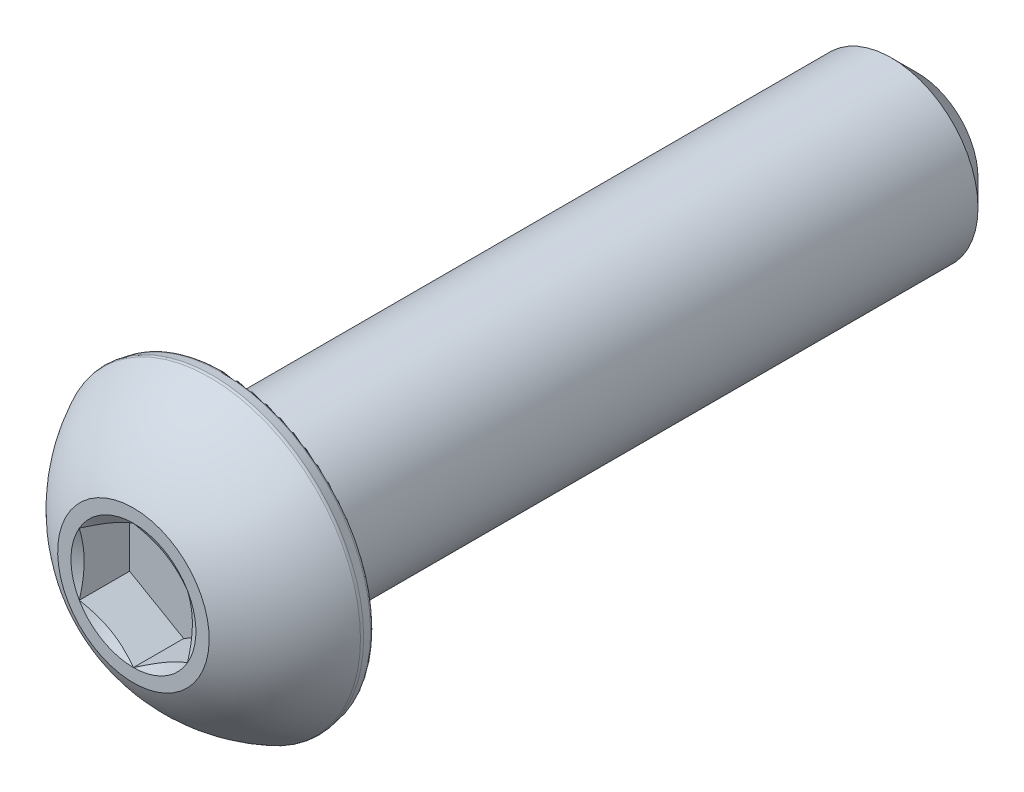
SolidWorks part; units mm, degrees
material "Cast Alloy Steel"
ref_plane "Front Plane" through (0, 0, 0) normal (0, 0, 1) x (1, 0, 0)
ref_plane "Top Plane" through (0, 0, 0) normal (0, 1, 0) x (1, 0, 0)
ref_plane "Right Plane" through (0, 0, 0) normal (1, 0, 0) x (0, 0, -1)
sketch "Sketch1" plane through (0, 0, 0) normal (1, 0, 0) x (0, 0, -1)
  line L0 (-14.3764, 0) -> (14.3764, 0) construction
  line L1 (-14.3764, 0) -> (-14.3764, 5.5499)
  line L2 (-14.3764, 5.5499) -> (-11.0236, 5.5499)
  line L3 (-11.0236, 5.5499) -> (-11.0236, 3.175)
  line L4 (-11.0236, 3.175) -> (14.3764, 3.175)
  line L5 (14.3764, 3.175) -> (14.3764, 0)
  point P2 (0, 0)
  point P4 (13.1064, 0)
  point P9 (12.4714, 3.175)
  point P10 (12.4714, -3.175)
  point P11 (14.3764, -3.175)
  point P15 (-12.5324, 0)
  dimension "Head Height" = 3.3528
  dimension "Head Diameter" = 11.0998
  dimension "Length" = 25.4
  dimension "Screw Size Decimal Equivalent" = 6.35
  dimension "Thread Pitch" = 1.27
  dimension "D1" = 1.905
  dimension "D2" = 1.844
sketch "Sketch2" plane through (0, 0, 0) normal (0, 0, 1) x (1, 0, 0)
  line L0 (0, 3.175) -> (0, 0) construction
  line L1 (0, 2.2914) -> (-1.9844, 1.1457)
  line L2 (-1.9844, 1.1457) -> (-1.9844, -1.1457)
  line L3 (-1.9844, -1.1457) -> (0, -2.2914)
  line L4 (0, -2.2914) -> (1.9844, -1.1457)
  line L5 (1.9844, -1.1457) -> (1.9844, 1.1457)
  line L6 (1.9844, 1.1457) -> (0, 2.2914)
  circle A0 centre (0, 0) radius 1.9844 construction
  circle A1 centre (0, 0) radius 2.7781
  point P10 (0, 2.7781)
  dimension "D1" = 5.5563
  dimension "Drive Size" = 3.9688
sketch "Sketch3" plane through (0, 0, 0) normal (1, 0, 0) x (0, 0, -1)
  line L0 (-14.3764, 0) -> (-14.3764, 2.7781)
  line L1 (-14.3764, 0) -> (-14.3764, 5.5499) construction
  line L2 (-14.3764, 5.5499) -> (-11.0236, 5.5499) construction
  line L3 (-11.5265, 5.5499) -> (-11.0236, 5.4612)
  line L4 (-11.0236, 5.5499) -> (-11.0236, 3.175) construction
  line L5 (-11.0236, 5.4612) -> (-11.0236, 3.175)
  line L6 (-14.3764, 0) -> (14.3764, 0) construction
  line L7 (-14.3764, 0) -> (14.3764, 0)
  line L8 (14.3764, 0) -> (14.3764, 2.2225)
  line L9 (14.3764, 3.175) -> (14.3764, 0) construction
  line L10 (14.3764, 2.2225) -> (13.4239, 3.175)
  line L11 (-11.0236, 3.175) -> (14.3764, 3.175) construction
  line L12 (13.4239, 3.175) -> (-11.0236, 3.175)
  arc A0 (-14.3764, 2.7781) -> (-11.5265, 5.5499) centre (-8.9016, 0) cw
  dimension "D1" = 0.5029
  dimension "D2" = 10
  dimension "D3" = 45
  dimension "D4" = 0.9525
revolve "Revolve1" add sketch "Sketch3" angle 360 about L7
sketch "Sketch4" plane through (0, 0, 14.3764) normal (0, 0, 1) x (1, 0, 0)
  line L0 (-1.9844, -1.1457) -> (0, -2.2914) construction
  line L1 (-1.9844, 1.1457) -> (-1.9844, -1.1457) construction
  line L2 (0, 2.2914) -> (-1.9844, 1.1457) construction
  line L3 (1.9844, 1.1457) -> (0, 2.2914) construction
  line L4 (1.9844, -1.1457) -> (1.9844, 1.1457) construction
  line L5 (0, -2.2914) -> (1.9844, -1.1457) construction
  line L6 (-1.9844, -1.1457) -> (0, -2.2914)
  line L7 (-1.9844, 1.1457) -> (-1.9844, -1.1457)
  line L8 (0, 2.2914) -> (-1.9844, 1.1457)
  line L9 (1.9844, 1.1457) -> (0, 2.2914)
  line L10 (1.9844, -1.1457) -> (1.9844, 1.1457)
  line L11 (0, -2.2914) -> (1.9844, -1.1457)
extrude "Cut-Extrude1" cut sketch "Sketch4" against normal up to vertex (1.844 mm away) up to point (0, 0, 12.5324)
sketch "Sketch5" plane through (0, 0, 14.3764) normal (0, 0, 1) x (1, 0, 0)
  circle A0 centre (0, 0) radius 2.2914
extrude "Cut-Extrude2" cut sketch "Sketch5" against normal up to vertex (1.844 mm away) draft 60 up to point (0, 0, 12.5324)
fillet "Fillet1" radius 0.1676 2 edges at (5.5499, 0, 11.5265) (5.4612, 0, 11.0236)
split "Split1" [suppressed] bodies to split 106
sketch "Sketch6" [suppressed] plane through (0, 0, -14.3764) normal (0, 0, -1) x (-1, 0, 0)
  circle A0 centre (0, 0) radius 3.175 construction
  circle A1 centre (0, 0) radius 3.175
curve "Helix/Spiral1" [suppressed] pitch 1.27 height 26.67 turns 21
sketch "Sketch7" [suppressed] plane through (0, 0, 0) normal (1, 0, 0) x (0, 0, -1)
  line L0 (14.297, 3.3125) -> (14.932, 2.2126) construction
  line L1 (14.932, 2.2126) -> (15.567, 3.3125) construction
  line L2 (15.567, 3.3125) -> (14.297, 3.3125) construction
  line L3 (14.3367, 3.2437) -> (15.5273, 3.2437)
  line L4 (15.5273, 3.2437) -> (15.0114, 2.3501)
  line L5 (15.0114, 2.3501) -> (14.8527, 2.3501)
  line L6 (14.8527, 2.3501) -> (14.3367, 3.2437)
  line L7 (14.932, 2.3501) -> (14.932, 2.2126) construction
  line L8 (14.3764, 3.175) -> (15.4877, 3.175) construction
  line L9 (14.932, 3.3125) -> (14.932, 3.175) construction
  point P12 (14.932, 3.2437)
  dimension "D1" = 1.27
  dimension "D2" = 0.1588
sweep "Cut-Sweep1" [suppressed] cut profiles "Sketch7" path "Helix/Spiral1"
sketch "Sketch8" [suppressed] plane through (0, 0, 11.0236) normal (0, 0, -1) x (-1, 0, 0)
  circle A0 centre (0, 0) radius 3.3125
extrude "Boss-Extrude1" [suppressed] add sketch "Sketch8" along normal up to vertex draft 45
equation "\"D1@Sketch1\"=\"Thread Pitch@Sketch1\"*1.5"
equation "\"D2@Sketch1\"=0.55*\"Head Height@Sketch1\""
equation "\"D1@Sketch2\"=\"Drive Size@Sketch2\"*1.4"
equation "\"D1@Sketch3\"=0.15*\"Head Height@Sketch1\""
equation "\"D4@Sketch3\"=0.75*\"Thread Pitch@Sketch1\""
equation "\"D1@Fillet1\"=.05*\"Head Height@Sketch1\""
equation "\"D4@Helix/Spiral1\"=\"Thread Pitch@Sketch1\""
equation "\"D3@Helix/Spiral1\"=\"Length@Sketch1\"+\"Thread Pitch@Sketch1\""
equation "\"D2@Sketch7\"=\"D1@Sketch7\"/8"
equation "\"D1@Sketch7\"=\"Thread Pitch@Sketch1\""
